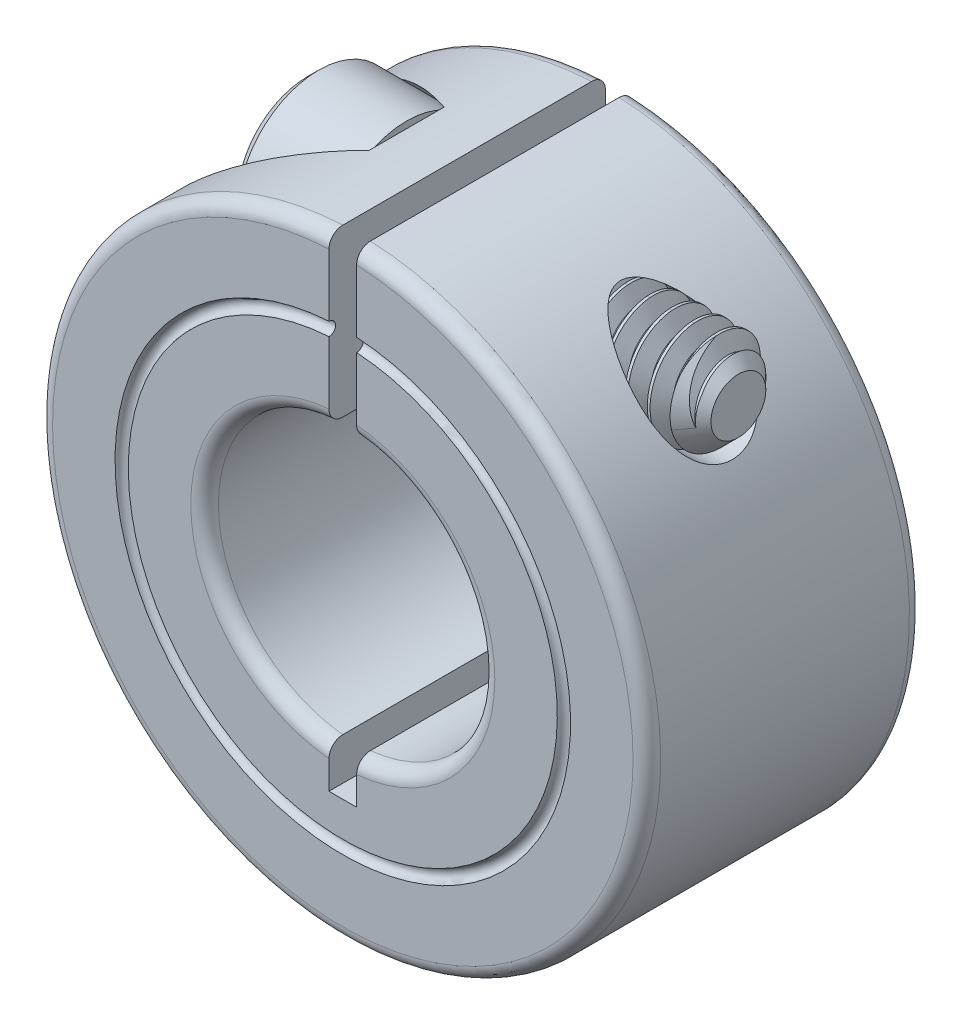
SolidWorks part; units mm, degrees
ref_plane "Front Plane" through (0, 0, 0) normal (0, 0, 1) x (1, 0, 0)
ref_plane "Top Plane" through (0, 0, 0) normal (0, 1, 0) x (1, 0, 0)
ref_plane "Right Plane" through (0, 0, 0) normal (1, 0, 0) x (0, 0, -1)
sketch "Sketch1" plane through (0, 0, 0) normal (0, 0, 1) x (1, 0, 0)
  line L0 (-0.3969, 3.9489) -> (-0.3969, 8.7222)
  line L2 (0.3969, 3.9489) -> (0.3969, 8.7222)
  line L3 (0, 0) -> (0, 3.9489) construction
  line L4 (0.3969, 3.9489) -> (-0.3969, 3.9489) construction
  line L5 (0, -8.7312) -> (0, -3.9688) construction
  line L6 (0, -3.9688) -> (0, -6.35) construction
  line L7 (-0.3969, -3.9489) -> (-0.3969, -5.1594)
  line L8 (-0.3969, -5.1594) -> (0.3969, -5.1594)
  line L9 (0.3969, -3.9489) -> (0.3969, -5.1594)
  line L10 (-0.3969, 6.3355) -> (0.3969, 6.3355) construction
  circle A0 centre (0, 0) radius 8.7312 construction
  circle A1 centre (0, 0) radius 3.9688 construction
  arc A3 (-0.3969, 8.7222) -> (0.3969, 8.7222) centre (0, 0) ccw
  arc A4 (0.3969, -3.9489) -> (0.3969, 3.9489) centre (0, 0) ccw
  arc A5 (-0.3969, 3.9489) -> (-0.3969, -3.9489) centre (0, 0) ccw
  point P4 (8.7312, 0)
  point P5 (-8.7312, 0)
  point P19 (0, -5.1594)
  dimension "Bore Dia" = 7.9375
  dimension "OD" = 17.4625
  dimension "Separation" = 0.7937
extrude "Extrude1" add sketch "Sketch1" along normal mid plane 7.9375
fillet "Fillet1" radius 0.3969 6 edges at (0, -8.7312, -3.9688) (0, -8.7312, 3.9688) (-3.9688, 0, -3.9688) (-3.9688, 0, 3.9688) (3.9688, 0, -3.9688) (3.9688, 0, 3.9688)
sketch "Sketch2" plane through (0, 0, 0) normal (0, 1, 0) x (1, 0, 0)
  line L0 (0, 0) -> (-3.9687, 0) construction
  line L1 (-3.9687, 0) -> (-8.7312, 0) construction
  line L2 (-6.35, 3.9688) -> (-6.35, -3.9688) construction
  line L3 (8.3344, 3.9688) -> (-8.3344, 3.9688) construction
  line L4 (-8.3344, -3.9688) -> (8.3344, -3.9688) construction
  line L5 (-8.7312, 3.5719) -> (-8.7312, -3.5719) construction
  line L6 (-3.9688, 3.5719) -> (-3.9688, -3.5719) construction
  line L8 (-6.5405, -3.9688) -> (-6.1595, -3.9688)
  line L9 (0, 3.9688) -> (0, -3.9688) construction
  line L10 (-0.3969, 3.9688) -> (-4.3656, 3.9688) construction
  arc A1 (-6.1595, -3.9688) -> (-6.5405, -3.9688) centre (-6.35, -3.9688) ccw
  point P1 (-6.35, 0)
  dimension "D2" = 0.1905
revolve "Cut-Revolve1" cut sketch "Sketch2" angle 360 about L9
sketch "Sketch3" plane through (0, 0, 0) normal (0, 0, 1) x (1, 0, 0)
  line L0 (8.7312, 6.3355) -> (-8.7312, 6.3355)
  line L1 (-8.7312, 6.3355) -> (-8.7312, 3.9479)
  line L2 (-8.7312, 3.9479) -> (-2.1336, 3.9479)
  line L4 (-2.1336, 3.9479) -> (-2.1336, 4.9131)
  line L7 (-2.1336, 4.9131) -> (8.7312, 4.9131)
  line L8 (8.7312, 4.9131) -> (8.7312, 6.3355)
  line L9 (-8.7312, 6.3355) -> (-11.1189, 6.3355) construction
  line L10 (-0.3969, 6.3355) -> (0.3969, 6.3355) construction
  dimension "D4" = 4.7752
  dimension "D2" = 2.1336
revolve "Cut-Revolve2" cut sketch "Sketch3" angle 360 about L9
sketch "Sketch4" plane through (0, 0, 0) normal (0, 0, 1) x (1, 0, 0)
  line L0 (-4.9784, 6.3355) -> (-4.9784, 8.6596)
  line L2 (-4.9784, 8.6596) -> (-2.1336, 8.6596)
  line L3 (-2.1336, 8.6596) -> (-2.1336, 7.7579)
  line L4 (-2.1336, 7.7579) -> (7.3914, 7.7579)
  line L5 (-2.1336, 3.9479) -> (-2.1336, 4.9131) construction
  line L6 (7.3914, 7.7579) -> (7.3914, 6.3355)
  line L7 (-2.1336, 4.9131) -> (8.7312, 4.9131) construction
  line L8 (7.3914, 6.3355) -> (-4.9784, 6.3355)
  line L9 (7.3914, 7.7579) -> (7.3914, 4.9131) construction
  line L10 (-4.9784, 6.3355) -> (-7.3025, 6.3355) construction
  line L11 (-8.7312, 6.3355) -> (-11.1189, 6.3355) construction
  dimension "Head Dia" = 4.6482
revolve "Revolve1" add sketch "Sketch4" angle 360 about L8
sketch "Sketch5" plane through (-4.9784, 0, 0) normal (-1, 0, 0) x (0, -1, 0)
  line L1 (-5.6481, -1.1906) -> (-4.9607, 0)
  line L2 (-4.9607, 0) -> (-5.6481, 1.1906)
  line L3 (-5.6481, 1.1906) -> (-7.0229, 1.1906)
  line L4 (-7.0229, 1.1906) -> (-7.7104, 0)
  line L5 (-7.7104, 0) -> (-7.0229, -1.1906)
  line L6 (-7.0229, -1.1906) -> (-5.6481, -1.1906)
  circle A0 centre (-6.3355, 0) radius 1.1906 construction
  dimension "Hex" = 2.3813
extrude "Cut-Extrude1" cut sketch "Sketch5" against normal blind 2.3813
chamfer "Chamfer1" distance 0.3175 angle 45 1 edges at (-4.9784, 8.6596, 0)
sketch "Sketch6" plane through (7.3914, 0, 0) normal (1, 0, 0) x (0, 1, 0)
  circle A0 centre (6.3355, 0) radius 1.4224 construction
  circle A1 centre (6.3355, 0) radius 1.4224
  point P3 (7.7579, 0)
curve "Helix/Spiral1" pitch 0.635 height 9.525 turns 15 parameters "Height"=9.525, "Pitch"=0.635
sketch "Sketch7" plane through (0, 0, 0) normal (0, 0, 1) x (1, 0, 0)
  line L0 (7.6692, 7.2768) -> (7.3517, 7.8267) construction
  line L1 (7.3517, 7.8267) -> (7.9867, 7.8267) construction
  line L2 (7.9867, 7.8267) -> (7.6692, 7.2768) construction
  line L3 (7.3914, 7.7579) -> (7.947, 7.7579) construction
  line L4 (7.6295, 7.3455) -> (7.7089, 7.3455)
  line L5 (7.6692, 7.8267) -> (7.6692, 7.7579) construction
  line L6 (7.6692, 7.3455) -> (7.6692, 7.2768) construction
  line L7 (7.6295, 7.3455) -> (7.3716, 7.7923)
  line L8 (7.3716, 7.7923) -> (7.9669, 7.7923)
  line L9 (7.9669, 7.7923) -> (7.7089, 7.3455)
  point P10 (7.6692, 7.7923)
  dimension "D1" = 0.635
  dimension "D2" = 0.0794
chamfer "Chamfer2" distance 0.635 angle 45 1 edges at (7.3914, 7.7579, 0)
sweep "Cut-Sweep1" cut profiles "Sketch7" path "Helix/Spiral1"
equation "\"D1@Sketch3\" = \"Screw Dia@Sketch3\""
equation "\"D1@Cut-Extrude1\" = \"Hex@Sketch5\""
equation "\"D1@Fillet1\" = \"Width@Extrude1\"*.05"
equation "\"D4@Sketch3\" = \"Head Dia@Sketch4\" + .005"
equation "\"Height@Helix/Spiral1\" = \"Screw Lg@Sketch4\""
equation "\"D1@Sketch7\" = \"Pitch@Helix/Spiral1\""
equation "\"D2@Sketch7\" = \"D1@Sketch7\"/8"
equation "\"D1@Chamfer2\" = \"Pitch@Helix/Spiral1\""
equation "\"Separation@Sketch1\" = \"Bore Dia@Sketch1\"/10"
equation "\"D2@Sketch3\" = \"Screw Dia@Sketch3\"*.750"
